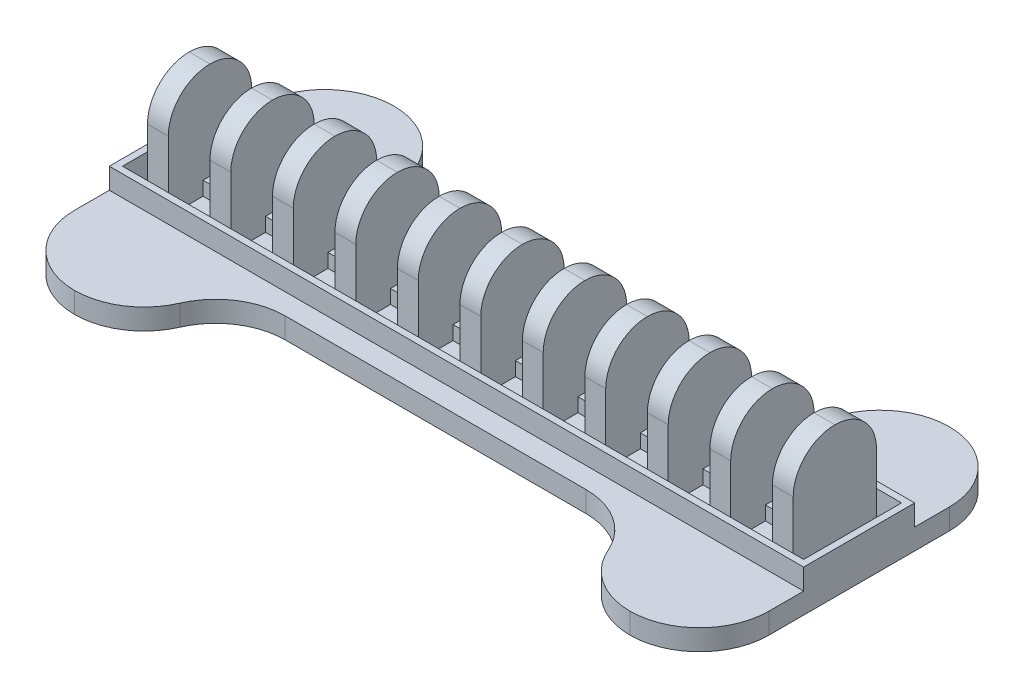
SolidWorks part; units mm, degrees
ref_plane "Front Plane" through (0, 0, 0) normal (0, 0, 1) x (1, 0, 0)
ref_plane "Top Plane" through (0, 0, 0) normal (0, 1, 0) x (1, 0, 0)
ref_plane "Right Plane" through (0, 0, 0) normal (1, 0, 0) x (0, 0, -1)
sketch "Sketch1" plane through (0, 0, 0) normal (0, 1, 0) x (1, 0, 0)
  line L1 (0, 0) -> (100, 0)
  line L2 (0, 0) -> (0, 16)
  line L3 (0, 16) -> (100, 16)
  line L4 (100, 0) -> (100, 16)
  dimension "D1" = 16
  dimension "D2" = 100
extrude "Boss-Extrude1" add sketch "Sketch1" along normal blind 3
sketch "Sketch2" plane through (0, 3, 0) normal (0, 1, 0) x (1, 0, 0)
  line L0 (0, 16) -> (0, 0) construction
  line L1 (1, 1) -> (99, 1)
  line L2 (1, 1) -> (1, 15)
  line L3 (1, 15) -> (99, 15)
  line L4 (99, 1) -> (99, 15)
  line L5 (100, 16) -> (0, 16) construction
  line L6 (0, 0) -> (100, 0) construction
  line L7 (100, 0) -> (100, 16) construction
  dimension "D1" = 1
  dimension "D2" = 1
  dimension "D3" = 1
  dimension "D4" = 1
extrude "Cut-Extrude1" cut sketch "Sketch2" against normal blind 1
sketch "Sketch5" plane through (0, 0, 0) normal (0, 0, 1) x (1, 0, 0)
  line L0 (0, 0) -> (100, 0) construction
  line L1 (0, 3) -> (20, 3)
  line L2 (0, 3) -> (0, 0)
  line L3 (0, 0) -> (20, 0)
  line L4 (20, 3) -> (20, 0)
  line L6 (100, 3) -> (80, 3)
  line L7 (100, 3) -> (100, 0)
  line L8 (100, 0) -> (80, 0)
  line L9 (80, 3) -> (80, 0)
  dimension "D1" = 20
  dimension "D2" = 20
extrude "Boss-Extrude4" add sketch "Sketch5" along normal blind 15
sketch "Sketch6" plane through (0, 0, -16) normal (0, 0, -1) x (-1, 0, 0)
  line L0 (-100, 0) -> (0, 0) construction
  line L1 (-100, 3) -> (-80, 3)
  line L2 (-100, 3) -> (-100, 0)
  line L3 (-100, 0) -> (-80, 0)
  line L4 (-80, 3) -> (-80, 0)
  line L6 (0, 3) -> (-20, 3)
  line L7 (0, 3) -> (0, 0)
  line L8 (0, 0) -> (-20, 0)
  line L9 (-20, 3) -> (-20, 0)
  dimension "D1" = 20
  dimension "D2" = 20
extrude "Boss-Extrude5" add sketch "Sketch6" along normal blind 15
fillet "Fillet18" radius 10 8 edges at (20, 1.5, 15) (0, 1.5, 15) (80, 1.5, 15) (100, 1.5, 15) (0, 1.5, -31) (20, 1.5, -31) (80, 1.5, -31) (100, 1.5, -31)
sketch "Sketch7" plane through (0, 2, 0) normal (0, 1, 0) x (1, 0, 0)
  line L0 (99, 1) -> (99, 15) construction
  line L1 (96.5, 2) -> (93.5, 2)
  line L2 (96.5, 2) -> (96.5, 14)
  line L3 (96.5, 14) -> (93.5, 14)
  line L4 (93.5, 2) -> (93.5, 14)
  line L5 (1, 1) -> (99, 1) construction
  line L6 (87.5, 2) -> (87.5, 14)
  line L7 (87.5, 2) -> (84.5, 2)
  line L8 (84.5, 2) -> (84.5, 14)
  line L9 (87.5, 14) -> (84.5, 14)
  line L10 (78.5, 2) -> (78.5, 14)
  line L11 (78.5, 2) -> (75.5, 2)
  line L12 (75.5, 2) -> (75.5, 14)
  line L13 (78.5, 14) -> (75.5, 14)
  line L14 (69.5, 2) -> (69.5, 14)
  line L15 (69.5, 2) -> (66.5, 2)
  line L16 (66.5, 2) -> (66.5, 14)
  line L17 (69.5, 14) -> (66.5, 14)
  line L18 (60.5, 2) -> (60.5, 14)
  line L19 (60.5, 2) -> (57.5, 2)
  line L20 (57.5, 2) -> (57.5, 14)
  line L21 (60.5, 14) -> (57.5, 14)
  line L22 (51.5, 2) -> (51.5, 14)
  line L23 (51.5, 2) -> (48.5, 2)
  line L24 (48.5, 2) -> (48.5, 14)
  line L25 (51.5, 14) -> (48.5, 14)
  line L26 (42.5, 2) -> (42.5, 14)
  line L27 (42.5, 2) -> (39.5, 2)
  line L28 (39.5, 2) -> (39.5, 14)
  line L29 (42.5, 14) -> (39.5, 14)
  line L30 (33.5, 2) -> (33.5, 14)
  line L31 (33.5, 2) -> (30.5, 2)
  line L32 (30.5, 2) -> (30.5, 14)
  line L33 (33.5, 14) -> (30.5, 14)
  line L34 (24.5, 2) -> (24.5, 14)
  line L35 (24.5, 2) -> (21.5, 2)
  line L36 (21.5, 2) -> (21.5, 14)
  line L37 (24.5, 14) -> (21.5, 14)
  line L38 (15.5, 2) -> (15.5, 14)
  line L39 (15.5, 2) -> (12.5, 2)
  line L40 (12.5, 2) -> (12.5, 14)
  line L41 (15.5, 14) -> (12.5, 14)
  line L42 (6.5, 2) -> (6.5, 14)
  line L43 (6.5, 2) -> (3.5, 2)
  line L44 (3.5, 2) -> (3.5, 14)
  line L45 (6.5, 14) -> (3.5, 14)
  line L46 (96.5, 2) -> (87.5, 2) construction
  dimension "D1" = 12
  dimension "D2" = 3
  dimension "D3" = 2.5
  dimension "D4" = 1
  dimension "D6" = 9
  dimension "D5" = 11
extrude "Boss-Extrude6" add sketch "Sketch7" along normal blind 16
sketch "Sketch8" plane through (0, 2, 0) normal (0, 1, 0) x (1, 0, 0)
  line L0 (93.5, 14) -> (93.5, 2) construction
  line L1 (93.5, 7) -> (87.5, 7)
  line L2 (93.5, 7) -> (93.5, 9)
  line L3 (93.5, 9) -> (87.5, 9)
  line L4 (87.5, 7) -> (87.5, 9)
  line L5 (87.5, 2) -> (87.5, 14) construction
  line L6 (99, 15) -> (1, 15) construction
  line L8 (84.5, 7) -> (84.5, 9)
  line L9 (84.5, 7) -> (78.5, 7)
  line L10 (78.5, 7) -> (78.5, 9)
  line L11 (84.5, 9) -> (78.5, 9)
  line L12 (75.5, 7) -> (75.5, 9)
  line L13 (75.5, 7) -> (69.5, 7)
  line L14 (69.5, 7) -> (69.5, 9)
  line L15 (75.5, 9) -> (69.5, 9)
  line L16 (66.5, 7) -> (66.5, 9)
  line L17 (66.5, 7) -> (60.5, 7)
  line L18 (60.5, 7) -> (60.5, 9)
  line L19 (66.5, 9) -> (60.5, 9)
  line L20 (57.5, 7) -> (57.5, 9)
  line L21 (57.5, 7) -> (51.5, 7)
  line L22 (51.5, 7) -> (51.5, 9)
  line L23 (57.5, 9) -> (51.5, 9)
  line L24 (48.5, 7) -> (48.5, 9)
  line L25 (48.5, 7) -> (42.5, 7)
  line L26 (42.5, 7) -> (42.5, 9)
  line L27 (48.5, 9) -> (42.5, 9)
  line L28 (39.5, 7) -> (39.5, 9)
  line L29 (39.5, 7) -> (33.5, 7)
  line L30 (33.5, 7) -> (33.5, 9)
  line L31 (39.5, 9) -> (33.5, 9)
  line L32 (30.5, 7) -> (30.5, 9)
  line L33 (30.5, 7) -> (24.5, 7)
  line L34 (24.5, 7) -> (24.5, 9)
  line L35 (30.5, 9) -> (24.5, 9)
  line L36 (21.5, 7) -> (21.5, 9)
  line L37 (21.5, 7) -> (15.5, 7)
  line L38 (15.5, 7) -> (15.5, 9)
  line L39 (21.5, 9) -> (15.5, 9)
  line L40 (12.5, 7) -> (12.5, 9)
  line L41 (12.5, 7) -> (6.5, 7)
  line L42 (6.5, 7) -> (6.5, 9)
  line L43 (12.5, 9) -> (6.5, 9)
  line L44 (93.5, 7) -> (84.5, 7) construction
  dimension "D1" = 2
  dimension "D2" = 6
  dimension "D3" = 10
  dimension "D4" = 9
extrude "Boss-Extrude7" add sketch "Sketch8" along normal blind 2
fillet "Fillet19" radius 6 22 edges at (95, 18, -2) (95, 18, -14) (86, 18, -2) (86, 18, -14) (77, 18, -2) (77, 18, -14) (68, 18, -2) (68, 18, -14) (59, 18, -2) (59, 18, -14) (50, 18, -2) (50, 18, -14) (41, 18, -2) (41, 18, -14) (32, 18, -2) (32, 18, -14) (23, 18, -14) (23, 18, -2) (14, 18, -2) (14, 18, -14) (5, 18, -2) (5, 18, -14)
sketch "Sketch10" plane through (0, 0, -16) normal (0, 0, -1) x (-1, 0, 0)
  line L1 (-80, 3) -> (-20, 3)
  line L2 (-80, 3) -> (-80, 0)
  line L3 (-80, 0) -> (-20, 0)
  line L4 (-20, 3) -> (-20, 0)
extrude "Boss-Extrude8" add sketch "Sketch10" along normal blind 3
sketch "Sketch11" plane through (0, 0, 0) normal (0, 0, 1) x (1, 0, 0)
  line L1 (20, 3) -> (80, 3)
  line L2 (20, 3) -> (20, 0)
  line L3 (20, 0) -> (80, 0)
  line L4 (80, 3) -> (80, 0)
extrude "Boss-Extrude9" add sketch "Sketch11" along normal blind 3
sketch "Sketch12" plane through (0, 3, 0) normal (0, 1, 0) x (1, 0, 0)
  line L0 (100, -5) -> (100, 21) construction
  line L1 (100, 14.9979) -> (99.05, 14.9979)
  line L2 (100, 14.9979) -> (100, 0.9979)
  line L3 (100, 0.9979) -> (99.05, 0.9979)
  line L4 (99.05, 14.9979) -> (99.05, 0.9979)
  line L5 (0, 21) -> (0, -5) construction
  line L6 (0, 14.9979) -> (0.95, 14.9979)
  line L7 (0, 14.9979) -> (0, 0.9979)
  line L8 (0, 0.9979) -> (0.95, 0.9979)
  line L9 (0.95, 14.9979) -> (0.95, 0.9979)
  dimension "D1" = 0.95
  dimension "D2" = 14
  dimension "D3" = 0.95
  dimension "D4" = 14
extrude "Boss-Extrude10" add sketch "Sketch12" along normal blind 3
sketch "Sketch13" plane through (0, 3, 0) normal (0, 1, 0) x (1, 0, 0)
  line L0 (0, 21) -> (0, 14.9979) construction
  line L1 (0, 15.05) -> (100, 15.05)
  line L2 (0, 15.05) -> (0, 16)
  line L3 (0, 16) -> (100, 16)
  line L4 (100, 15.05) -> (100, 16)
  line L5 (100, 14.9979) -> (100, 21) construction
  line L6 (100, -5) -> (100, 0.9979) construction
  line L7 (0, 0) -> (100, 0)
  line L8 (0, 0) -> (0, 0.95)
  line L9 (0, 0.95) -> (100, 0.95)
  line L10 (100, 0) -> (100, 0.95)
  line L11 (99, 15) -> (1, 15) construction
  line L13 (1, 1) -> (99, 1) construction
  dimension "D1" = 0.95
  dimension "D2" = 0.05
  dimension "D3" = 0.05
extrude "Boss-Extrude11" add sketch "Sketch13" along normal blind 3
sketch "Sketch14" plane through (0, 3, 0) normal (0, 1, 0) x (1, 0, 0)
  line L0 (0.95, 14.9979) -> (0, 14.9979) construction
  line L1 (0, 15.05) -> (0.95, 15.05)
  line L2 (0, 15.05) -> (0, 14.9979)
  line L3 (0, 14.9979) -> (0.95, 14.9979)
  line L4 (0.95, 15.05) -> (0.95, 14.9979)
  line L5 (0.95, 14.9979) -> (0, 14.9979) construction
extrude "Boss-Extrude12" add sketch "Sketch14" along normal blind 3
sketch "Sketch15" plane through (0, 3, 0) normal (0, 1, 0) x (1, 0, 0)
  line L0 (100, 0.95) -> (0, 0.95) construction
  line L1 (0, 0.9979) -> (0.95, 0.9979)
  line L2 (0, 0.9979) -> (0, 0.95)
  line L3 (0, 0.95) -> (0.95, 0.95)
  line L4 (0.95, 0.9979) -> (0.95, 0.95)
  line L6 (100, 0.9979) -> (99.0503, 0.9979)
  line L7 (100, 0.9979) -> (100, 0.95)
  line L8 (100, 0.95) -> (99.0503, 0.95)
  line L9 (99.0503, 0.9979) -> (99.0503, 0.95)
  line L10 (100, 15.05) -> (99.05, 15.05)
  line L11 (100, 15.05) -> (100, 14.9979)
  line L12 (100, 14.9979) -> (99.05, 14.9979)
  line L13 (99.05, 15.05) -> (99.05, 14.9979)
extrude "Boss-Extrude13" add sketch "Sketch15" along normal blind 3
ref_plane "Plane1" through (0, 6, 0) normal (0, 0, 1) x (1, 0, 0)
fillet "Fillet20" radius 10 4 edges at (20, 1.5, -19) (80, 1.5, -19) (80, 1.5, 3) (20, 1.5, 3)
sketch "Sketch17" plane through (0, 6, 0) normal (0, 1, 0) x (1, 0, 0)
  line L0 (0.95, 15.05) -> (0.95, 0.95)
  line L1 (0.95, 15.05) -> (99.05, 15.05)
  line L2 (0.95, 0.95) -> (99.05, 0.95)
  line L3 (99.05, 15.05) -> (99.05, 0.95)
  line L4 (99.05, 15.05) -> (99.05, 0.9979) construction
  line L5 (1.45, 14.55) -> (1.45, 1.45)
  line L6 (1.45, 1.45) -> (98.55, 1.45)
  line L7 (98.55, 14.55) -> (98.55, 1.45)
  line L8 (1.45, 14.55) -> (98.55, 14.55)
  dimension "D1" = 0.5
extrude "Cut-Extrude2" cut sketch "Sketch17" against normal blind 4
